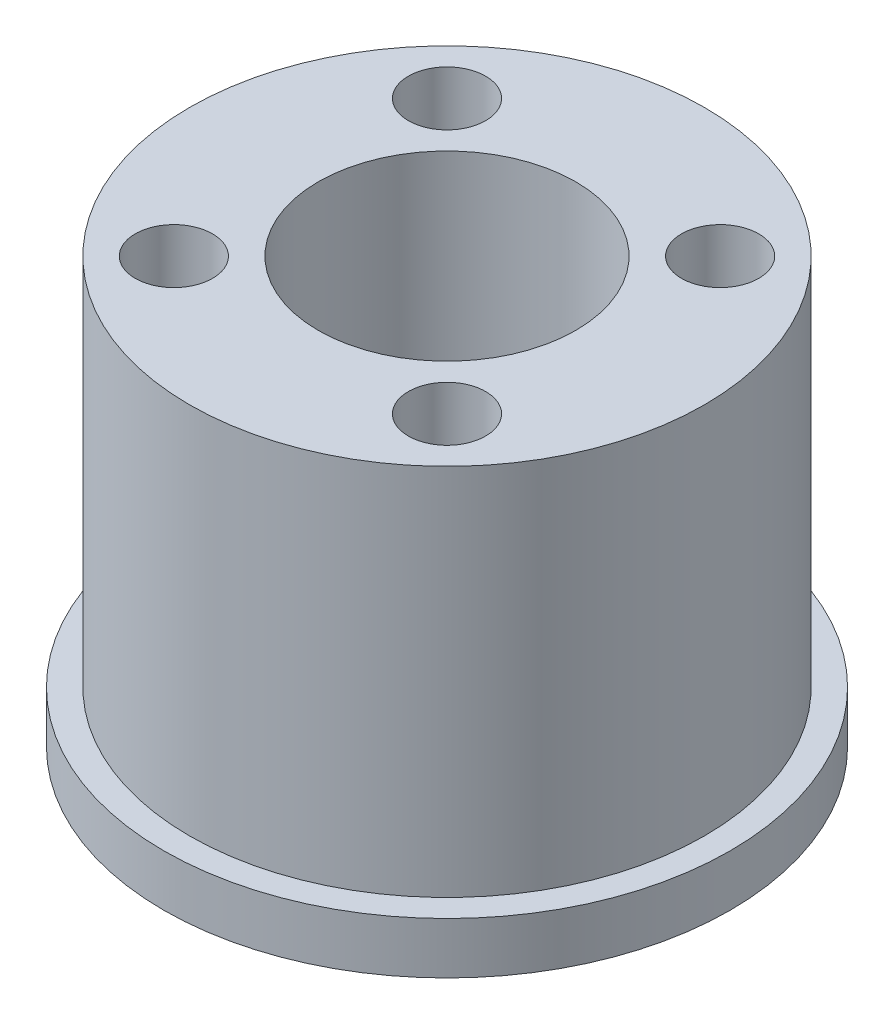
SolidWorks part; units mm, degrees
ref_plane "前视基准面" through (0, 0, 0) normal (0, 0, 1) x (1, 0, 0)
ref_plane "上视基准面" through (0, 0, 0) normal (0, 1, 0) x (1, 0, 0)
ref_plane "右视基准面" through (0, 0, 0) normal (1, 0, 0) x (0, 0, -1)
sketch "草图1" plane through (0, 0, 0) normal (0, 0, 1) x (1, 0, 0)
  line L0 (11, 2) -> (0, 2)
  line L1 (0, 2) -> (0, 0)
  line L2 (0, 0) -> (11, 0)
  line L3 (11, 0) -> (11, 2)
  line L4 (0, 2) -> (0, 0) construction
revolve "旋转1" add sketch "草图1" angle 360 about L4 reverse direction yes
sketch "草图2" plane through (0, 2, 0) normal (0, 1, 0) x (-1, 0, 0)
  circle A0 centre (0, 0) radius 10
extrude "凸台-拉伸1" add sketch "草图2" along normal blind 14.5
hole_wizard "Ø3.0 (3) 直径孔1" positions "草图4" profile "草图3" hole size "Ø3.0" standard "ANSI Metric"
sketch "草图4" plane through (0, 16.5, 0) normal (0, 1, 0) x (1, 0, 0)
  point P0 (5.3033, 5.3033)
  point P1 (5.3033, -5.3033)
  point P2 (-5.3033, -5.3033)
  point P3 (-5.3033, 5.3033)
sketch "草图3" plane through (5.3033, 16.5, -5.3033) normal (1, 0, 0) x (0, 0, 1)
  line L0 (0, 0) -> (0, 6)
  line L1 (0, 6) -> (1.5, 6)
  line L2 (1.5, 6) -> (1.5, 0)
  line L5 (1.5, 0) -> (0, 0)
  line L10 (0, 6) -> (-1.5, 6) construction
  line L11 (0, -6.35) -> (0, 107.95) construction
  dimension "孔直径" = 3
  dimension "孔深度" = 6
  dimension "导头角度" = 180
hole_wizard "Ø10.0 (10) 直径孔1" positions "草图6" profile "草图5" hole size "Ø10.0" standard "ANSI Metric"
sketch "草图6" plane through (0, 0, 0) normal (0, -1, 0) x (-1, 0, 0)
  point P0 (0, 0)
sketch "草图5" plane through (0, 0, 0) normal (1, 0, 0) x (0, 0, -1)
  line L0 (0, 0) -> (0, 16.5)
  line L1 (0, 16.5) -> (5, 16.5)
  line L2 (5, 16.5) -> (5, 0)
  line L5 (5, 0) -> (0, 0)
  line L11 (0, -6.35) -> (0, 107.95) construction
  dimension "通孔孔直径" = 10
  dimension "通孔孔深度" = 16.5
